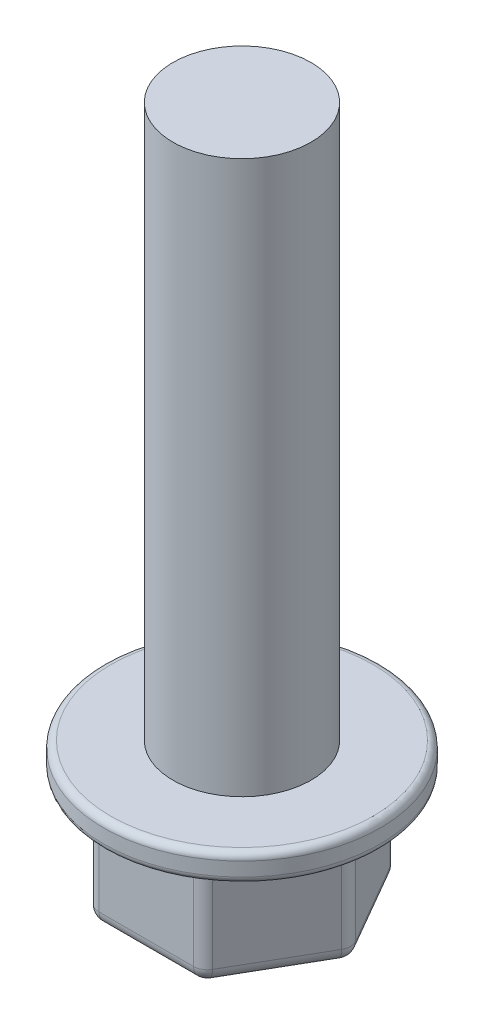
SolidWorks part; units mm, degrees
material "AISI 4140 Steel, quenched & tempered"
ref_plane "Front Plane" through (0, 0, 0) normal (1, 0, 0) x (0, 1, 0)
ref_plane "Top Plane" through (0, 0, 0) normal (0, 0, 1) x (0, 1, 0)
ref_plane "Right Plane" through (0, 0, 0) normal (0, 1, 0) x (-1, 0, 0)
sketch "Sketch1" plane through (0, 0, 0) normal (1, 0, 0) x (0, 1, 0)
  line L0 (-41.7852, 0) -> (49.5775, 0) construction
  line L1 (0, 32.8217) -> (0, -34.113) construction
  line L2 (0, 5) -> (40, 5)
  line L3 (40, 5) -> (40, 0)
  line L4 (0, 5) -> (0, 10)
  line L5 (0, 10) -> (-2, 10)
  line L6 (-2, 10) -> (-2, 0)
  line L7 (-2, 0) -> (40, 0)
  dimension "D1" = 40
  dimension "D2" = 10
  dimension "D3" = 20
  dimension "D4" = 2
revolve "Revolve1" add sketch "Sketch1" angle 360 about L0
sketch "Sketch2" plane through (0, -2, 0) normal (0, -1, 0) x (1, 0, 0)
  line L1 (4, -6.9282) -> (8, 0)
  line L2 (8, 0) -> (4, 6.9282)
  line L3 (4, 6.9282) -> (-4, 6.9282)
  line L4 (-4, 6.9282) -> (-8, 0)
  line L5 (-8, 0) -> (-4, -6.9282)
  line L6 (-4, -6.9282) -> (4, -6.9282)
  circle A0 centre (0, 0) radius 6.9282 construction
  circle A1 centre (0, 0) radius 5.5
  circle A2 centre (0, 0) radius 3
  dimension "D1" = 8
  dimension "D2" = 6
  dimension "D3" = 11
extrude "Boss-Extrude1" add sketch "Sketch2" along normal blind 8 contours L4 L5 L6 L1 L2 L3
extrude "Cut-Extrude1" cut sketch "Sketch2<3>" against normal blind 1 from surface contours A1 A2 region at (-5.3444, -2, 0) starting at face at (0, -10, 0)
sketch "Sketch2<3>" plane through (0, -2, 0) normal (0, -1, 0) x (1, 0, 0) same geometry as "Sketch2"
fillet "Fillet1" radius 1 18 edges at (-6, -2, -3.4641) (0, -2, -6.9282) (-6, -2, 3.4641) (6, -2, -3.4641) (0, -2, 6.9282) (6, -2, 3.4641) (0, -10, 6.9282) (-6, -10, 3.4641) (-6, -10, -3.4641) (0, -10, -6.9282) (6, -10, -3.4641) (6, -10, 3.4641) (4, -6, 6.9282) (8, -6, 0) (-4, -6, -6.9282) (-8, -6, 0) (-4, -6, 6.9282) (4, -6, -6.9282)
fillet "Fillet2" radius 0.5 5 edges at (0, -10, -5.5) (0, 0, -10) (0, -2, -10) (0, -9, -3) (0, -10, -3)
fillet "Fillet3" radius 0.5 1 edges at (0, -9, -5.5)
